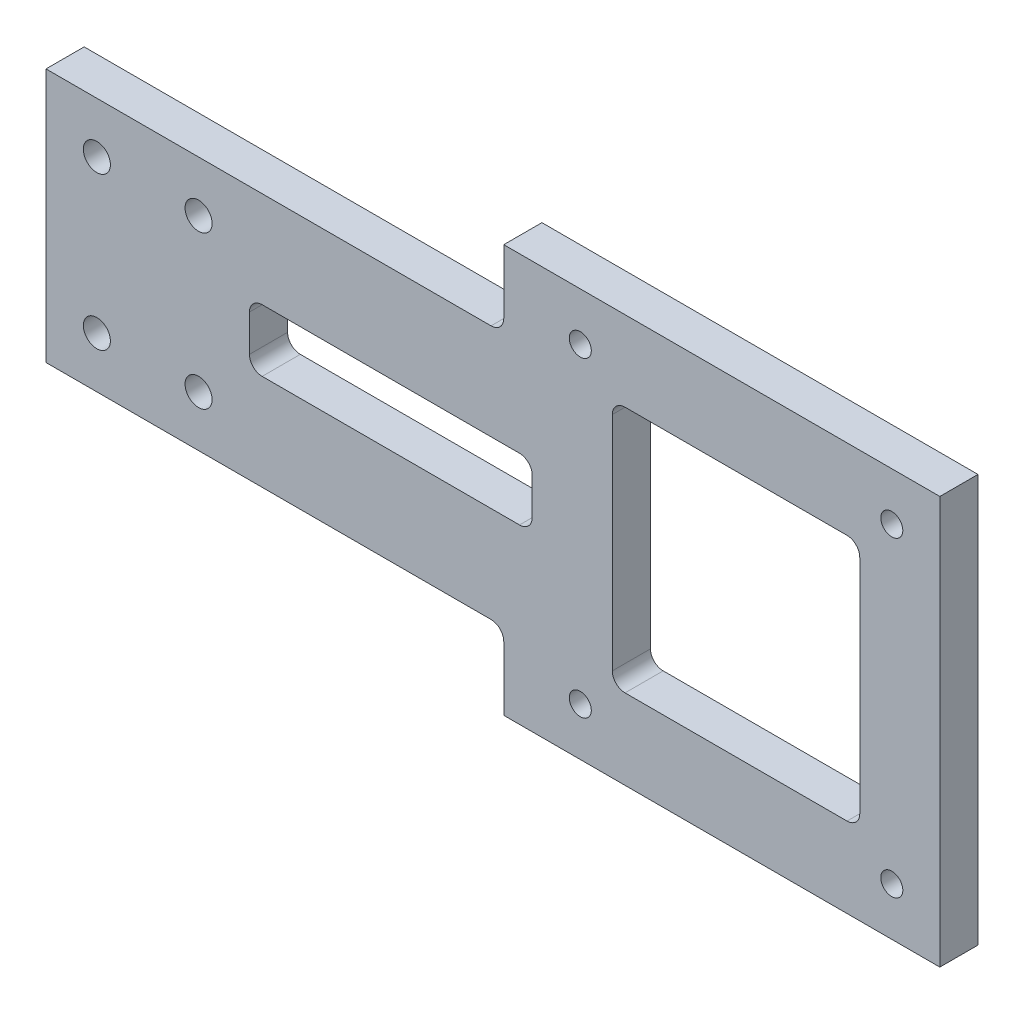
SolidWorks part; units mm, degrees
material "6061-T6 (SS)"
ref_plane "Front" through (0, 0, 0) normal (0, 0, 1) x (1, 0, 0)
ref_plane "Top" through (0, 0, 0) normal (0, 1, 0) x (1, 0, 0)
ref_plane "Right" through (0, 0, 0) normal (1, 0, 0) x (0, 0, -1)
sketch "Sketch1" plane through (0, 0, 0) normal (0, 0, 1) x (1, 0, 0)
  line L0 (82.55, 31.75) -> (82.55, 50.8909)
  line L1 (82.55, 31.75) -> (-31.75, 31.75)
  line L3 (82.55, -31.75) -> (-31.75, -31.75)
  line L4 (-31.75, 31.75) -> (-31.75, -31.75)
  line L5 (-31.75, -31.75) -> (0, 0) construction
  line L6 (0, 0) -> (-31.75, 31.75) construction
  line L7 (82.55, 50.8909) -> (191.4409, 50.8909)
  line L8 (191.4409, 50.8909) -> (191.4409, 30.8909)
  line L9 (191.4409, 30.8909) -> (109.6591, 30.8909)
  line L10 (109.6591, 30.8909) -> (109.6591, -30.8909)
  line L11 (109.6591, -30.8909) -> (191.4409, -30.8909)
  line L12 (191.4409, -30.8909) -> (191.4409, -50.8909)
  line L13 (191.4409, -50.8909) -> (82.55, -50.8909)
  line L14 (82.55, -50.8909) -> (82.55, -31.75)
  line L15 (179.4409, -30.8909) -> (179.4409, -38.8909) construction
  line L16 (179.4409, -38.8909) -> (179.4409, -50.8909) construction
  line L17 (0, 0) -> (140.55, 0) construction
  line L18 (179.4409, -38.8909) -> (101.6591, 38.8909) construction
  line L19 (179.4409, 38.8909) -> (101.6591, -38.8909) construction
  line L20 (109.6591, 30.8909) -> (140.55, 0) construction
  line L21 (140.55, 0) -> (109.6591, -30.8909) construction
  line L22 (179.4409, 38.8909) -> (179.4409, 50.8909) construction
  line L23 (179.4409, 38.8909) -> (191.4409, 38.8909) construction
  line L24 (179.4409, 38.8909) -> (179.4409, 30.8909) construction
  line L25 (101.6591, 38.8909) -> (82.55, 38.8909) construction
  line L26 (0, 0) -> (109.6591, 0) construction
  line L27 (0, 0) -> (82.55, -31.75) construction
  line L28 (0, 0) -> (82.55, 31.75) construction
  line L29 (179.4409, -38.8909) -> (191.4409, -38.8909) construction
  line L30 (140.55, 0) -> (140.55, 30.8909) construction
  line L31 (140.55, 0) -> (109.6591, 0) construction
  circle A0 centre (140.55, 0) radius 55 construction
  point P0 (0, 0)
  point P17 (179.4409, 38.8909)
  point P18 (179.4409, -38.8909)
  point P19 (101.6591, 38.8909)
  point P20 (101.6591, -38.8909)
  dimension "D2" = 110
  dimension "D1" = 63.5
  dimension "D3" = 90
  dimension "D5" = 8
  dimension "D6" = 12
  dimension "D7" = 114.3
  dimension "D9" = 58
  dimension "D10" = 0
extrude "Boss-Extrude1" add sketch "Sketch1" along normal blind 9.525
hole_wizard "M5 Clearance Hole1" positions "Sketch3" profile "Sketch4" hole size "M5" standard "ANSI Metric"
sketch "Sketch3" plane through (0, 0, 9.525) normal (0, 0, 1) x (1, 0, 0)
  line L0 (0, 0) -> (140.55, 0) construction
  line L2 (179.4409, -38.8909) -> (101.6591, 38.8909) construction
  line L4 (179.4409, 38.8909) -> (101.6591, -38.8909) construction
  line L6 (109.6591, 30.8909) -> (140.55, 0) construction
  line L7 (140.55, 0) -> (109.6591, -30.8909) construction
  line L8 (82.55, 31.75) -> (-31.75, 31.75) construction
  line L12 (82.55, -31.75) -> (82.55, -50.8909) construction
  circle A0 centre (140.55, 0) radius 55 construction
  point P0 (179.4409, 38.8909)
  point P2 (179.4409, -38.8909)
  point P4 (101.6591, 38.8909)
  point P6 (101.6591, -38.8909)
  dimension "D1" = 110
  dimension "D2" = 135
  dimension "D3" = 90
  dimension "D4" = 58
sketch "Sketch4" plane through (179.4409, 38.8909, 9.525) normal (1, 0, 0) x (0, -1, 0)
  line L0 (0, 0) -> (0, 20.4024)
  line L1 (0, 20.4024) -> (2.75, 18.75)
  line L2 (2.75, 18.75) -> (2.75, 0)
  line L5 (2.75, 0) -> (0, 0)
  line L10 (0, 20.4024) -> (-2.75, 18.75) construction
  line L11 (0, -6.35) -> (0, 107.95) construction
  dimension "Hole Dia." = 5.5
  dimension "Hole Depth" = 18.75
  dimension "Drill Angle" = 118
fillet "Fillet1" radius 3.175 4 edges at (109.6591, 30.8909, 4.7625) (109.6591, -30.8909, 4.7625) (82.55, -31.75, 4.7625) (82.55, 31.75, 4.7625)
hole_wizard "1/4 Clearance Hole1" positions "Sketch5" profile "Sketch6" hole size "1/4" standard "ANSI Inch"
sketch "Sketch5" plane through (0, 0, 9.525) normal (0, 0, 1) x (1, 0, 0)
  line L0 (-19.05, 19.05) -> (6.35, 19.05) construction
  line L1 (6.35, 19.05) -> (6.35, -19.05) construction
  line L2 (6.35, -19.05) -> (-19.05, -19.05) construction
  line L3 (-19.05, -19.05) -> (-19.05, 19.05) construction
  line L5 (79.375, 31.75) -> (-31.75, 31.75) construction
  line L9 (-31.75, -31.75) -> (-19.05, -19.05) construction
  line L11 (-19.05, 19.05) -> (-31.75, 31.75) construction
  point P0 (-19.05, 19.05)
  point P2 (6.35, 19.05)
  point P4 (6.35, -19.05)
  point P6 (-19.05, -19.05)
  dimension "D1" = 12.7
  dimension "D2" = 25.4
sketch "Sketch6" plane through (-19.05, 19.05, 9.525) normal (1, 0, 0) x (0, -1, 0)
  line L0 (0, 0) -> (0, 20.7798)
  line L1 (0, 20.7798) -> (3.3782, 18.75)
  line L2 (3.3782, 18.75) -> (3.3782, 0)
  line L5 (3.3782, 0) -> (0, 0)
  line L10 (0, 20.7798) -> (-3.3782, 18.75) construction
  line L11 (0, -6.35) -> (0, 107.95) construction
  dimension "Hole Dia." = 6.7564
  dimension "Hole Depth" = 18.75
  dimension "Drill Angle" = 118
sketch "Sketch7" plane through (0, 0, 9.525) normal (0, 0, 1) x (1, 0, 0)
  line L0 (6.35, 19.05) -> (6.35, 31.75) construction
  line L1 (89.6591, -7.75) -> (19.05, -7.75)
  line L2 (89.6591, -7.75) -> (89.6591, 7.75)
  line L3 (89.6591, 7.75) -> (19.05, 7.75)
  line L4 (19.05, -7.75) -> (19.05, 7.75)
  line L5 (89.6591, -7.75) -> (19.05, 7.75) construction
  line L6 (89.6591, 7.75) -> (19.05, -7.75) construction
  line L7 (109.6591, -27.7159) -> (109.6591, 27.7159) construction
  line L8 (79.375, 31.75) -> (-31.75, 31.75) construction
  line L9 (0, 0) -> (54.3546, 0) construction
  line L10 (6.35, 19.05) -> (19.05, 19.05) construction
  point P0 (54.3546, 0)
  dimension "D1" = 20
  dimension "D2" = 24
extrude "Cut-Extrude1" cut sketch "Sketch7" against normal through all
fillet "Fillet2" radius 3.175 4 edges at (89.6591, -7.75, 4.7625) (89.6591, 7.75, 4.7625) (19.05, 7.75, 4.7625) (19.05, -7.75, 4.7625)
sketch "Sketch8" plane through (0, 0, 9.525) normal (0, 0, 1) x (1, 0, 0)
  line L0 (112.8341, 30.8909) -> (191.4409, 30.8909) construction
  line L1 (191.4409, -30.8909) -> (171.4409, -30.8909)
  line L2 (191.4409, -30.8909) -> (191.4409, 30.8909)
  line L3 (191.4409, 30.8909) -> (171.4409, 30.8909)
  line L4 (171.4409, -30.8909) -> (171.4409, 30.8909)
  line L5 (191.4409, -50.8909) -> (191.4409, -30.8909) construction
extrude "Boss-Extrude2" add sketch "Sketch8" against normal up to surface (9.525 mm away) up to face at (54.3546, 0, 0)
fillet "Fillet3" radius 3.175 2 edges at (171.4409, -30.8909, 4.7625) (171.4409, 30.8909, 4.7625)
sketch "Sketch10" plane through (0, 0, 9.525) normal (0, 0, 1) x (1, 0, 0)
  line L16 (79.375, 34.925) -> (-34.925, 34.925)
  line L17 (-34.925, -34.925) -> (79.375, -34.925)
  line L18 (-34.925, 34.925) -> (-34.925, -34.925)
  line L19 (79.375, 34.925) -> (-34.925, 34.925) construction
  line L20 (-34.925, -34.925) -> (79.375, -34.925) construction
  line L21 (-34.925, 34.925) -> (-34.925, -34.925) construction
  line L26 (86.4841, -4.575) -> (86.4841, 4.575)
  line L27 (86.4841, 4.575) -> (22.225, 4.575)
  line L28 (22.225, 4.575) -> (22.225, -4.575)
  line L29 (22.225, -4.575) -> (86.4841, -4.575)
  line L30 (86.4841, -4.575) -> (86.4841, 4.575) construction
  line L31 (86.4841, 4.575) -> (22.225, 4.575) construction
  line L32 (22.225, 4.575) -> (22.225, -4.575) construction
  line L33 (22.225, -4.575) -> (86.4841, -4.575) construction
  line L39 (79.375, -34.925) -> (79.375, -54.0659)
  line L40 (194.6159, -54.0659) -> (194.6159, 54.0659)
  line L41 (79.375, -54.0659) -> (194.6159, -54.0659)
  line L42 (194.6159, 54.0659) -> (79.375, 54.0659)
  line L43 (79.375, 54.0659) -> (79.375, 34.925)
  line L44 (79.375, -34.925) -> (79.375, -54.0659) construction
  line L45 (194.6159, -54.0659) -> (194.6159, 54.0659) construction
  line L46 (79.375, -54.0659) -> (194.6159, -54.0659) construction
  line L47 (194.6159, 54.0659) -> (79.375, 54.0659) construction
  line L48 (79.375, 54.0659) -> (79.375, 34.925) construction
  line L69 (112.8341, -27.7159) -> (168.2659, -27.7159)
  line L70 (168.2659, -27.7159) -> (168.2659, 27.7159)
  line L71 (168.2659, 27.7159) -> (112.8341, 27.7159)
  line L72 (112.8341, 27.7159) -> (112.8341, -27.7159)
  line L73 (112.8341, -27.7159) -> (168.2659, -27.7159) construction
  line L74 (168.2659, -27.7159) -> (168.2659, 27.7159) construction
  line L75 (168.2659, 27.7159) -> (112.8341, 27.7159) construction
  line L76 (112.8341, 27.7159) -> (112.8341, -27.7159) construction
  dimension "D1" = 3.175
  dimension "D2" = 3.175
  dimension "D3" = 3.175
  dimension "D4" = 3.175
